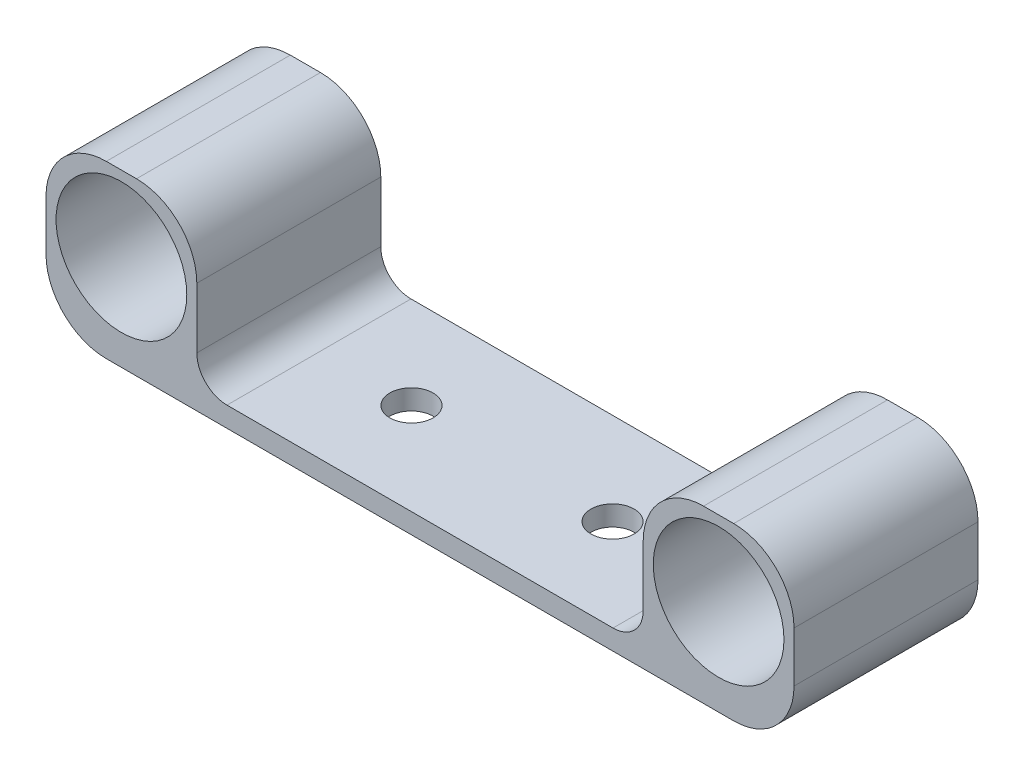
SolidWorks part; units mm, degrees
ref_plane "Front Plane" through (0, 0, 0) normal (0, 0, 1) x (1, 0, 0)
ref_plane "Top Plane" through (0, 0, 0) normal (0, 1, 0) x (1, 0, 0)
ref_plane "Right Plane" through (0, 0, 0) normal (1, 0, 0) x (0, 0, -1)
sketch "Sketch1" plane through (0, 0, 0) normal (0, 1, 0) x (1, 0, 0)
  line L0 (22.2, 18.3) -> (22.2, 0) construction
  line L1 (0, 0) -> (44.4, 0)
  line L2 (0, 0) -> (0, 18.3)
  line L3 (0, 18.3) -> (44.4, 18.3)
  line L4 (44.4, 0) -> (44.4, 18.3)
  line L5 (12.2, 9.15) -> (22.2, 9.15) construction
  line L6 (22.2, 9.15) -> (32.2, 9.15) construction
  line L8 (44.4, 0) -> (59.4, 0)
  line L9 (44.4, 0) -> (44.4, 18.3)
  line L10 (44.4, 18.3) -> (59.4, 18.3)
  line L11 (59.4, 0) -> (59.4, 18.3)
  line L12 (0, 0) -> (-15, 0)
  line L13 (0, 0) -> (0, 18.3)
  line L14 (0, 18.3) -> (-15, 18.3)
  line L15 (-15, 0) -> (-15, 18.3)
  circle A0 centre (12.2, 9.15) radius 2.15
  circle A1 centre (32.2, 9.15) radius 2.15
  dimension "D3" = 4.3
  dimension "D4" = 4.3
  dimension "D1" = 18.3
  dimension "D2" = 44.4
  dimension "D5" = 10
  dimension "D6" = 10
  dimension "D7" = 15
  dimension "D8" = 15
extrude "Boss-Extrude1" add sketch "Sketch1" along normal blind 2 contours L15 L12 L2 L14 | L1 L4 L3 L2 A1 A0 | L8 L11 L10 L4 region at (22.2, 0, -9.15) region at (-7.5, 0, -9.15) region at (51.9, 0, -9.15)
extrude "Boss-Extrude2" add sketch "Sketch1<3>" along normal blind 17 contours L8 L11 L10 L4 | L15 L12 L2 L14 region at (-7.5, 0, -9.15) region at (51.9, 0, -9.15)
sketch "Sketch1<3>" plane through (0, 0, 0) normal (0, 1, 0) x (1, 0, 0) same geometry as "Sketch1"
sketch "Sketch2" plane through (0, 0, 0) normal (0, 0, 1) x (1, 0, 0)
  line L0 (-15, 9.5) -> (0, 9.5) construction
  line L1 (0, 2) -> (-15, 2)
  line L2 (0, 2) -> (0, 17)
  line L3 (0, 17) -> (-15, 17)
  line L4 (-15, 2) -> (-15, 17)
  line L5 (44.4, 2) -> (59.4, 2)
  line L6 (44.4, 2) -> (44.4, 17)
  line L7 (44.4, 17) -> (59.4, 17)
  line L8 (59.4, 2) -> (59.4, 17)
  line L9 (44.4, 9.5) -> (59.4, 9.5) construction
  circle A0 centre (-7.5, 9.5) radius 6.5
  circle A1 centre (51.9, 9.5) radius 6.5
  dimension "D1" = 13
  dimension "D2" = 13
extrude "Cut-Extrude2" cut sketch "Sketch2" against normal offset from surface (12.315 mm away) 5.985 contours A0 | A1 up to face at (22.2, 9, -18.3)
fillet "Fillet3" radius 6 6 edges at (59.4, 0, -9.15) (59.4, 17, -9.15) (44.4, 17, -9.15) (-15, 0, -9.15) (0, 17, -9.15) (-15, 17, -9.15)
fillet "Fillet4" radius 3 2 edges at (44.4, 2, -9.15) (0, 2, -9.15)
